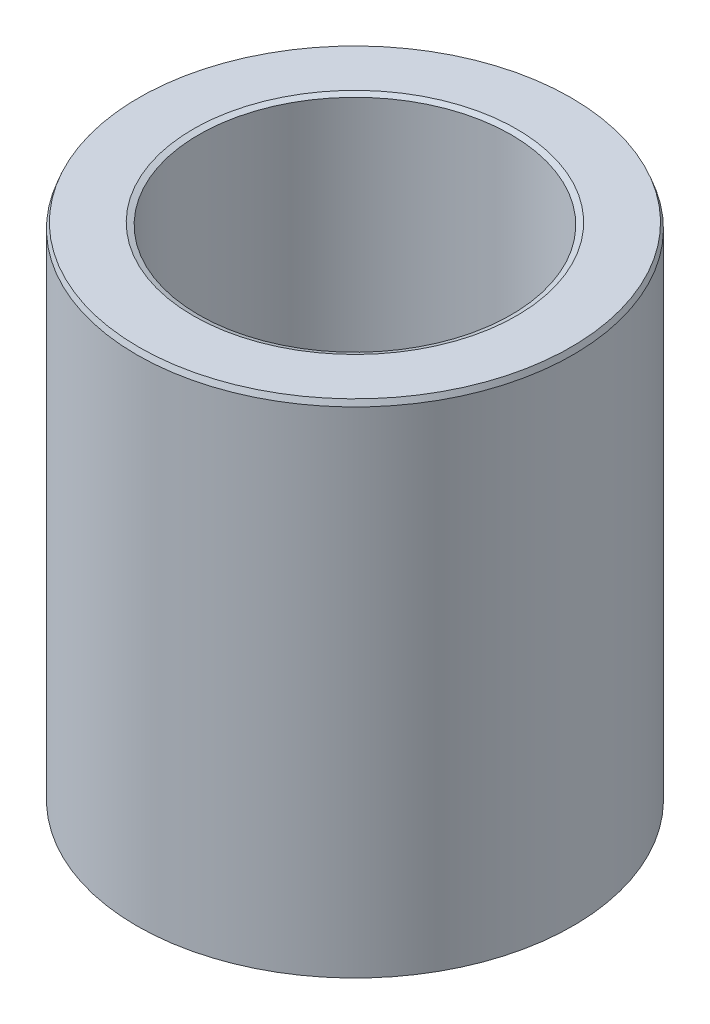
SolidWorks part; units mm, degrees
ref_plane "Front Plane" through (0, 0, 0) normal (0, 0, 1) x (1, 0, 0)
ref_plane "Top Plane" through (0, 0, 0) normal (0, 1, 0) x (1, 0, 0)
ref_plane "Right Plane" through (0, 0, 0) normal (1, 0, 0) x (0, 0, -1)
sketch "Sketch1" plane through (0, 0, 0) normal (0, 1, 0) x (1, 0, 0)
  circle A0 centre (0, 0) radius 15
  dimension "SLEEVE_OD" = 30
extrude "Boss-Extrude1" add sketch "Sketch1" along normal blind 34.5323
sketch "Sketch2" plane through (0, 0, 0) normal (0, 1, 0) x (1, 0, 0)
  circle A0 centre (0, 0) radius 10.7374
  dimension "BORE_D" = 21.4749
extrude "Cut-Extrude1" cut sketch "Sketch2" along normal through all
chamfer "Chamfer1" distance 0.3839 angle 20.257 4 edges at (0, 34.5323, 10.7374) (0, 0, 10.7374) (0, 0, 15) (0, 34.5323, 15) first distance on face at (0, 34.5323, 10.7374) first distance on face at (0, 0, 10.7374) first distance on face at (0, 34.5323, 15)
